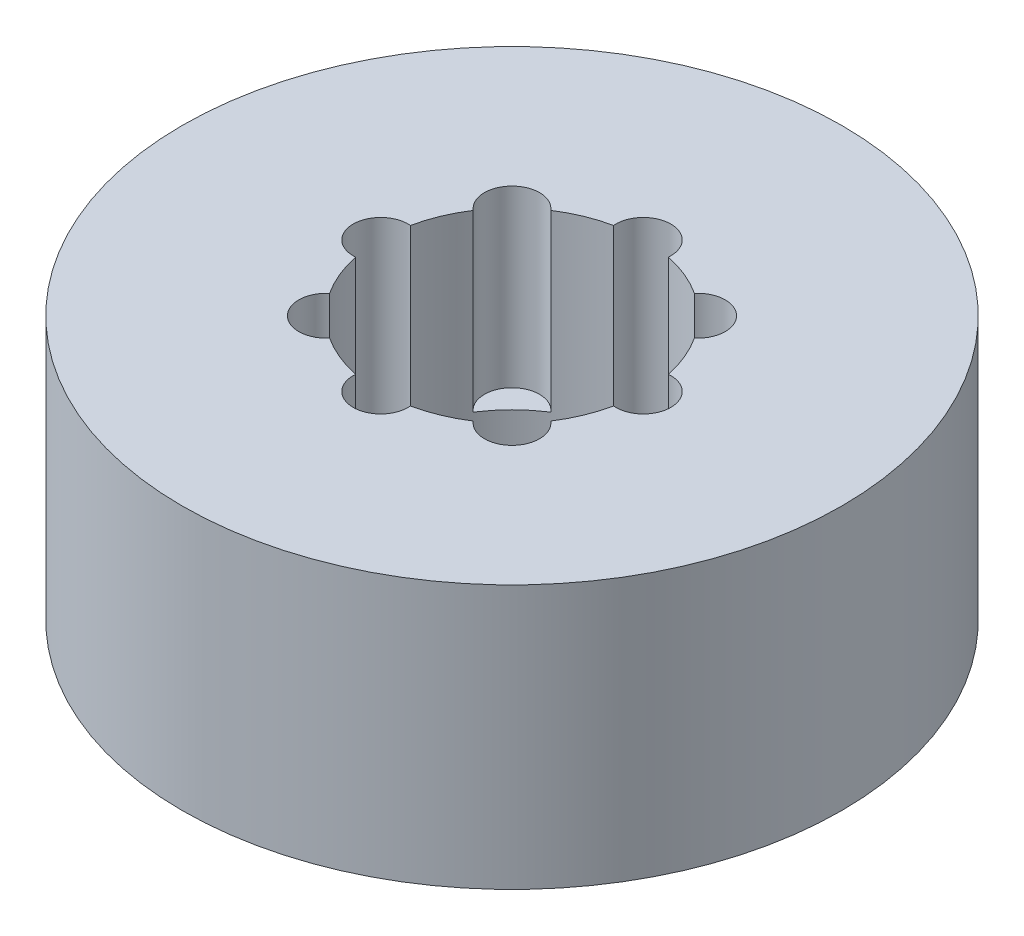
SolidWorks part; units mm, degrees
ref_plane "Front Plane" through (0, 0, 0) normal (0, 0, 1) x (1, 0, 0)
ref_plane "Top Plane" through (0, 0, 0) normal (0, 1, 0) x (1, 0, 0)
ref_plane "Right Plane" through (0, 0, 0) normal (1, 0, 0) x (0, 0, -1)
sketch "Sketch1" plane through (0, 0, 0) normal (0, 1, 0) x (1, 0, 0)
  circle A0 centre (0, 0) radius 25
  dimension "FLANGE_OD" = 50
extrude "Boss-Extrude1" add sketch "Sketch1" along normal blind 20
sketch "Sketch2" plane through (0, 0, 0) normal (0, 1, 0) x (1, 0, 0)
  circle A0 centre (0, 0) radius 10
  dimension "BORE_D" = 20
extrude "Cut-Extrude1" cut sketch "Sketch2" along normal through all
sketch "Sketch3" plane through (0, 20, 0) normal (0, 1, 0) x (1, 0, 0)
  circle A0 centre (0, 0) radius 9.9576 construction
  circle A1 centre (-9.9576, 0) radius 2.087
  dimension "BOLT_D" = 4.174
  dimension "BOLT_PCD" = 19.9151
extrude "Cut-Extrude2" cut sketch "Sketch3" against normal blind 13.245
pattern_circular "CirPattern1" count 8 over 360 about axis through (0, 0, 0) along (0, 1, 0) of "Cut-Extrude2"
